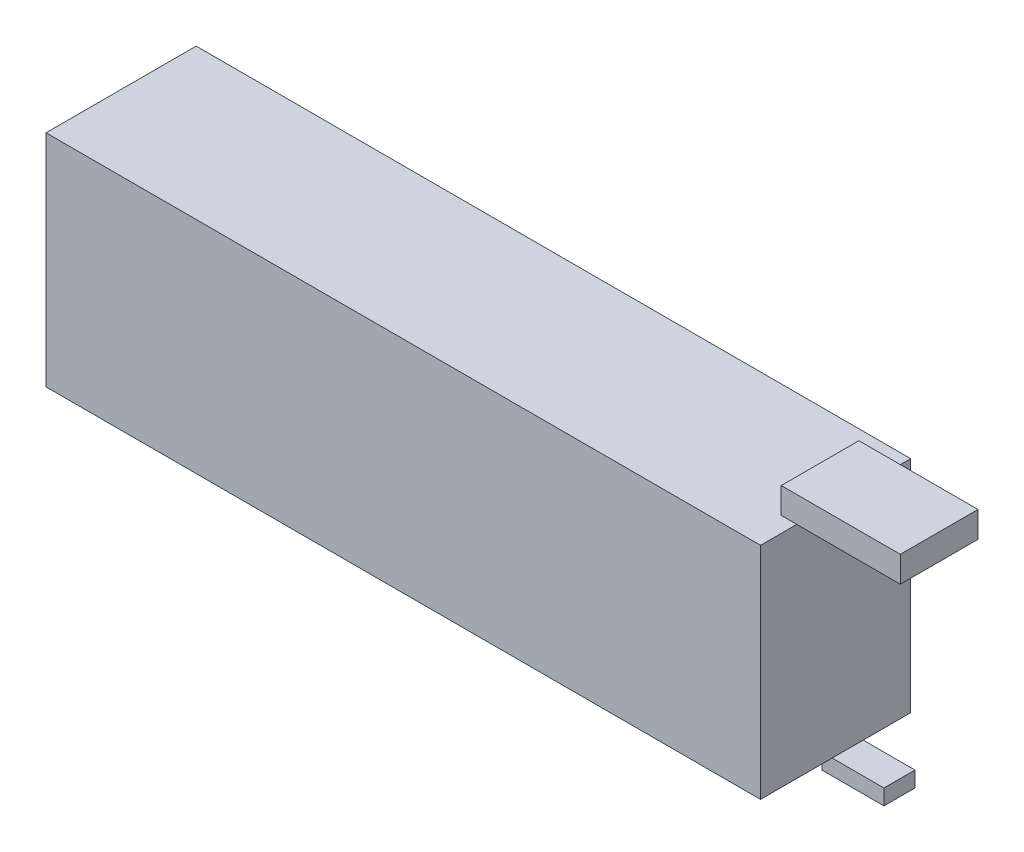
SolidWorks part; units mm, degrees
ref_plane "Front Plane" through (0, 0, 0) normal (0, 0, 1) x (1, 0, 0)
ref_plane "Top Plane" through (0, 0, 0) normal (0, 1, 0) x (1, 0, 0)
ref_plane "Right Plane" through (0, 0, 0) normal (1, 0, 0) x (0, 0, -1)
sketch "Sketch1" plane through (0, 0, 0) normal (0, 0, 1) x (1, 0, 0)
  line L1 (-69, 21.25) -> (69, 21.25)
  line L2 (-69, 21.25) -> (-69, -21.25)
  line L3 (-69, -21.25) -> (69, -21.25)
  line L4 (69, 21.25) -> (69, -21.25)
  line L5 (-69, 21.25) -> (69, -21.25) construction
  line L6 (-69, -21.25) -> (69, 21.25) construction
  point P0 (0, 0)
  dimension "D1" = 42.5
  dimension "D2" = 138
extrude "Boss-Extrude1" add sketch "Sketch1" along normal mid plane 29
sketch "Sketch2" plane through (0, 0, 0) normal (1, 0, 0) x (0, 0, -1)
  line L0 (-14.5, 21.25) -> (14.5, 21.25) construction
  line L1 (-7.5, 21.25) -> (7.5, 21.25)
  line L2 (-7.5, 21.25) -> (-7.5, 26.25)
  line L3 (-7.5, 26.25) -> (7.5, 26.25)
  line L4 (7.5, 21.25) -> (7.5, 26.25)
  line L5 (-7.5, 21.25) -> (7.5, 26.25) construction
  line L6 (-7.5, 26.25) -> (7.5, 21.25) construction
  line L7 (-0.6659, -21.25) -> (5.3341, -21.25)
  line L8 (-0.6659, -21.25) -> (-0.6659, -24.25)
  line L9 (-0.6659, -24.25) -> (5.3341, -24.25)
  line L10 (5.3341, -21.25) -> (5.3341, -24.25)
  line L11 (-0.6659, -21.25) -> (5.3341, -24.25) construction
  line L12 (-0.6659, -24.25) -> (5.3341, -21.25) construction
  line L13 (-14.5, -21.25) -> (14.5, -21.25) construction
  point P0 (0, 23.75)
  point P5 (2.3341, -22.75)
  point P12 (0, 0)
  point P16 (1.9925, -21.7516)
  dimension "D1" = 15
  dimension "D2" = 5
  dimension "D3" = 3
  dimension "D4" = 6
  dimension "D5" = 3
extrude "Boss-Extrude2" add sketch "Sketch2" along normal blind 20 and the other way blind 3 from surface contours L1 L4 L3 L2 region at (0, 23.75, 0) starting at face at (69, 0, 0)
extrude "Boss-Extrude3" add sketch "Sketch2<3>" along normal blind 10 and the other way blind 2 from surface contours L10 L7 L8 L9 region at (0, -22.75, -2.3341) starting at face at (69, 7.0833, 0)
sketch "Sketch2<3>" plane through (0, 0, 0) normal (1, 0, 0) x (0, 0, -1) same geometry as "Sketch2"
